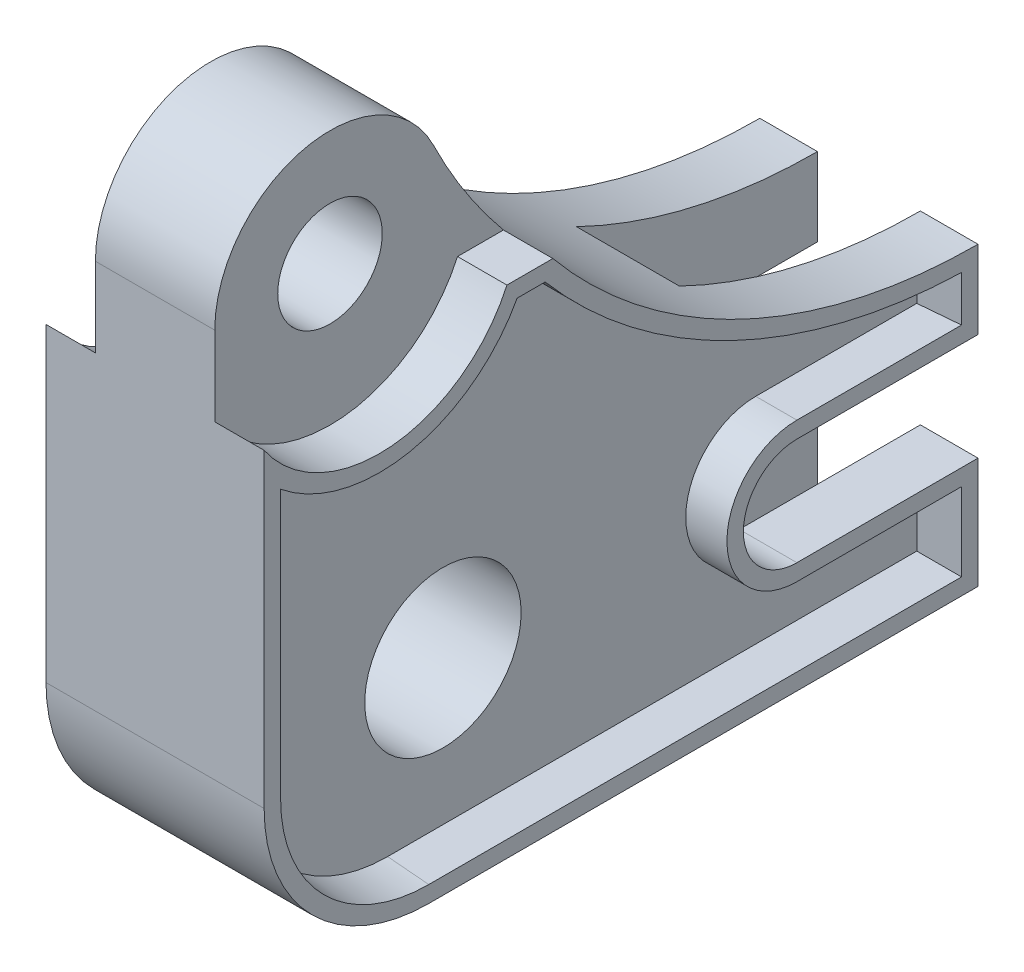
SolidWorks part; units mm, degrees
ref_plane "Front Plane" through (0, 0, 0) normal (0, 0, 1) x (1, 0, 0)
ref_plane "Top Plane" through (0, 0, 0) normal (0, 1, 0) x (1, 0, 0)
ref_plane "Right Plane" through (0, 0, 0) normal (1, 0, 0) x (0, 0, -1)
sketch "Sketch2" plane through (0, 0, 0) normal (1, 0, 0) x (0, 0, -1)
  line L0 (-44.0127, 24.5844) -> (-44.0127, -22.7362)
  line L1 (-24.0127, -42.7362) -> (42.7058, -42.7362)
  line L2 (42.7058, -42.7362) -> (42.7058, -29.2362)
  line L3 (42.7058, -29.2362) -> (20.7058, -29.2362)
  line L4 (20.7058, -16.2362) -> (42.7058, -16.2362)
  line L5 (42.7058, -16.2362) -> (42.7058, -6.7362)
  line L6 (-13.2795, 15.5844) -> (-9.8751, 15.5844)
  line L7 (40.7058, -14.2362) -> (40.7058, -8.7072)
  line L8 (20.7058, -14.2362) -> (40.7058, -14.2362)
  line L9 (40.7058, -31.2362) -> (20.7058, -31.2362)
  line L10 (40.7058, -40.7362) -> (40.7058, -31.2362)
  line L11 (-24.0127, -40.7362) -> (40.7058, -40.7362)
  line L13 (-14.5208, 17.5844) -> (-8.9417, 17.5844)
  line L14 (-14.5208, 17.5844) -> (-7.2217, 17.5844) construction
  line L15 (-13.2795, 15.5844) -> (-7.2217, 15.5844) construction
  line L16 (-42.0127, 9.8535) -> (-42.0127, -22.7362)
  line L17 (-42.0127, 24.5844) -> (-42.0127, -22.7362) construction
  arc A0 (-17.4441, 30.7512) -> (42.7058, -6.7362) centre (42.7058, 60.2638) ccw
  arc A2 (-17.4441, 30.7512) -> (-44.0127, 24.5844) centre (-30.0127, 24.5844) ccw
  circle A3 centre (-17.2942, -22.7362) radius 9.5
  arc A4 (20.7058, -16.2362) -> (20.7058, -29.2362) centre (20.7058, -22.7362) ccw
  circle A5 centre (-30.0127, 24.5844) radius 6.35
  arc A6 (-44.0127, -22.7362) -> (-24.0127, -42.7362) centre (-24.0127, -22.7362) ccw
  arc A7 (-42.0127, 9.8535) -> (-13.2795, 15.5844) centre (-30.0127, 24.5844) ccw
  arc A8 (-9.8751, 15.5844) -> (40.7058, -8.7072) centre (42.7058, 60.2638) ccw
  arc A9 (20.7058, -14.2362) -> (20.7058, -31.2362) centre (20.7058, -22.7362) ccw
  arc A10 (-42.0127, -22.7362) -> (-24.0127, -40.7362) centre (-24.0127, -22.7362) ccw
  arc A12 (-42.539, 13.0913) -> (-14.5208, 17.5844) centre (-30.0127, 24.5844) ccw
  arc A13 (-19.2396, 29.8703) -> (40.7058, -8.7072) centre (42.7058, 60.2638) ccw construction
  arc A14 (-19.2396, 29.8703) -> (-42.0127, 24.5844) centre (-30.0127, 24.5844) ccw construction
  arc A15 (-44.0127, 11.7392) -> (-13.2795, 15.5844) centre (-30.0127, 24.5844) ccw construction
  arc A16 (-44.0127, 14.9408) -> (-14.5208, 17.5844) centre (-30.0127, 24.5844) ccw
  point P38 (-153.3473, 48.5589)
  dimension "D1" = 134
  dimension "D2" = 28
  dimension "D3" = 12.7
  dimension "D4" = 19
  dimension "D5" = 13
  dimension "D11" = 20
  dimension "D14" = 34
  dimension "D6" = 49
  dimension "D7" = 22
  dimension "D8" = 36
  dimension "D9" = 60
  dimension "D10" = 20
  dimension "D12" = 2
extrude "Boss-Extrude1" add sketch "Sketch2" along normal mid plane 14.5 contours L0 A16 A12 L13 A0 A2 A5 region at (0, 37.7659, 33.0722)
extrude "Boss-Extrude2" add sketch "Sketch2<3>" along normal mid plane 26.5 contours A16 L0 A6 L1 L2 L3 A4 L4 L5 A0 L13 A12 A10 L16 A7 L6 A8 L7 L8 A9 L9 L10 L11 region at (0, 13.9246, 43.3907)
sketch "Sketch2<3>" plane through (0, 0, 0) normal (1, 0, 0) x (0, 0, -1) same geometry as "Sketch2"
extrude "Boss-Extrude3" add sketch "Sketch2<4>" along normal mid plane 16.5 contours L16 A10 L11 L10 L9 A9 L8 L7 A8 L6 A7 A3 region at (0, -16.7362, 6.9121)
sketch "Sketch2<4>" plane through (0, 0, 0) normal (1, 0, 0) x (0, 0, -1) same geometry as "Sketch2"
chamfer "Chamfer1" distance 5 angle 5 10 edges at (-13.25, -40.7362, -8.3465) (-13.25, -35.4641, 36.7406) (-13.25, -6.4413, 42.0127) (8.25, -40.7362, -8.3465) (8.25, -35.4641, 36.7406) (8.25, -6.4413, 42.0127) (-13.25, -35.9862, -40.7058) (-13.25, -11.4717, -40.7058) (8.25, -35.9862, -40.7058) (8.25, -11.4717, -40.7058) first distance on face at (-10.75, -40.7362, -8.3465) first distance on face at (-10.75, -33.6001, 34.8767) first distance on face at (-10.75, -6.4413, 42.0127) first distance on face at (10.75, -40.7362, -8.3465) first distance on face at (10.75, -33.6001, 34.8767) first distance on face at (10.75, -6.4413, 42.0127) first distance on face at (-10.75, -35.9862, -40.7058) first distance on face at (-10.75, -11.4717, -40.7058) first distance on face at (10.75, -35.9862, -40.7058) first distance on face at (10.75, -11.4717, -40.7058)
sketch "Sketch3" plane through (0, 0, 0) normal (0, 1, 0) x (1, 0, 0)
  line L0 (13.25, 42.7058) -> (-13.25, 42.7058) construction
  line L1 (6.25, 4.7058) -> (-6.25, 4.7058)
  line L2 (6.25, 4.7058) -> (6.25, 42.7058)
  line L3 (6.25, 42.7058) -> (-6.25, 42.7058)
  line L4 (-6.25, 4.7058) -> (-6.25, 42.7058)
  line L5 (0, -24.0127) -> (0, 42.7058) construction
  dimension "D1" = 38
  dimension "D2" = 12.5
  dimension "D3" = 6.25
extrude "Cut-Extrude1" cut sketch "Sketch3" against normal blind 50
equation "\"A\"= 60"
equation "\"B\"= 20"
equation "\"C\"= 26.5"
